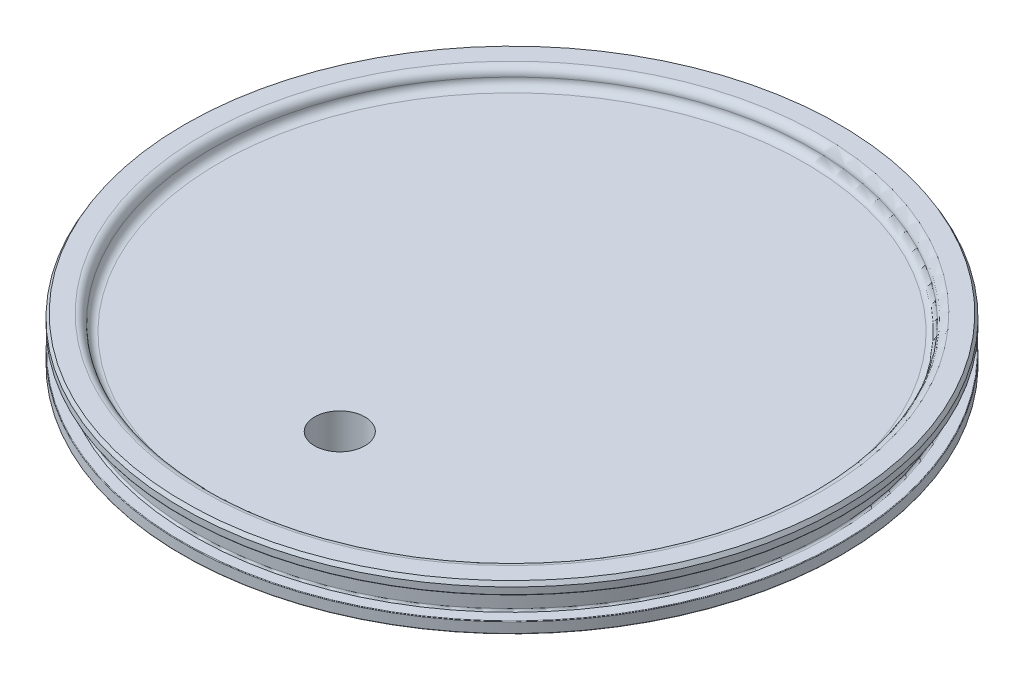
SolidWorks part; units mm, degrees
material "6061-T6 (SS)"
ref_plane "Front Plane" through (0, 0, 0) normal (0, 0, 1) x (1, 0, 0)
ref_plane "Top Plane" through (0, 0, 0) normal (0, 1, 0) x (1, 0, 0)
ref_plane "Right Plane" through (0, 0, 0) normal (1, 0, 0) x (0, 0, -1)
sketch "Sketch1" plane through (0, 0, 0) normal (0, 0, 1) x (1, 0, 0)
  line L0 (0, 48.1922) -> (0, -25.6743) construction
  line L1 (0, 0) -> (72.898, 0)
  line L2 (72.898, 0) -> (72.898, 2.4638)
  line L3 (72.898, 2.4638) -> (70.0532, 2.4638)
  line L4 (70.0532, 2.4638) -> (70.0532, 7.4422)
  line L5 (70.0532, 7.4422) -> (72.898, 7.4422)
  line L6 (72.898, 7.4422) -> (72.898, 9.906)
  line L7 (72.898, 9.906) -> (66.548, 9.906)
  line L8 (66.548, 9.906) -> (66.548, 6.35)
  line L9 (66.548, 6.35) -> (0, 6.35)
  line L10 (0, 6.35) -> (0, 0)
  dimension "D1" = 145.796
  dimension "D2" = 4.9784
  dimension "D3" = 2.8448
  dimension "D4" = 9.906
  dimension "D5" = 6.35
  dimension "D6" = 6.35
revolve "Revolve1" add sketch "Sketch1" angle 360 about L0
sketch "Sketch6" plane through (0, 0, 0) normal (0, -1, 0) x (1, 0, 0)
  circle A0 centre (0, 0) radius 66.04
  dimension "D1" = 132.08
extrude "Boss-Extrude1" add sketch "Sketch6" along normal blind 2.54
fillet "CNC ID Fillet" radius 0.4064 3 edges at (-70.0532, 7.4422, 0) (-70.0532, 2.4638, 0) (66.04, 0, 0)
fillet "CNC OD Fillet" radius 0.127 4 edges at (-72.898, 7.4422, 0) (-72.898, 2.4638, 0) (66.04, -2.54, 0) (-72.898, 0, 0)
chamfer "CNC Chamfers" distance 0.508 angle 60 1 edges at (-72.898, 9.906, 0) first distance on face at (-66.548, 9.906, 0)
fillet "CNC Bore Fillet" radius 1.778 2 edges at (-66.548, 6.35, 0) (-66.548, 9.906, 0)
hole_wizard "Pipe Tap Drill for 1/4 Tap - To Injector" positions "Sketch15" profile "Sketch16" hole size "1/4" standard "ANSI Inch" end condition through all
sketch "Sketch15" plane through (0, -2.54, 0) normal (0, -1, 0) x (-1, 0, 0)
  point P4 (0, -38.1)
  dimension "D1" = 38.1
sketch "Sketch16" plane through (0, -2.54, 38.1) normal (1, 0, 0) x (0, 0, -1)
  line L0 (0, 0) -> (0, 12.446)
  line L1 (0, 12.446) -> (5.5626, 12.446)
  line L2 (5.5626, 12.446) -> (5.5626, 0)
  line L5 (5.5626, 0) -> (0, 0)
  line L11 (0, -6.35) -> (0, 107.95) construction
  dimension "Thru Hole Dia." = 11.1252
  dimension "Thru Hole Depth" = 12.446
